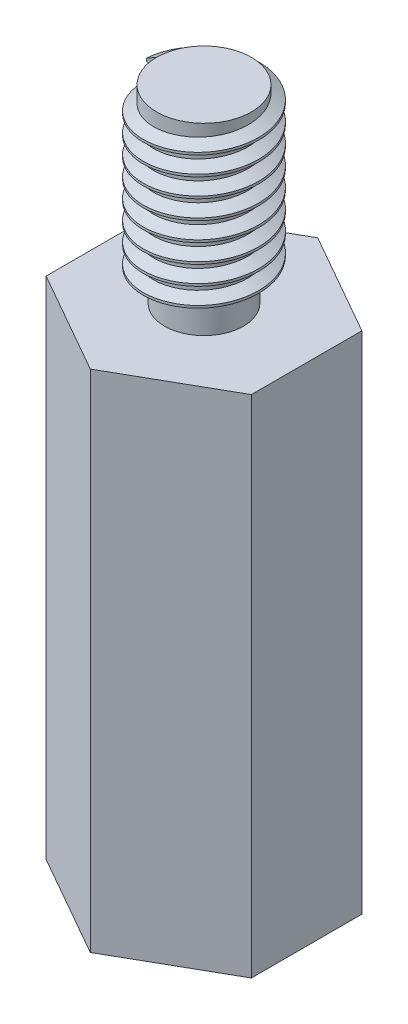
SolidWorks part; units mm, degrees
material "1.4000 (X6Cr13)"
ref_plane "Plan de face" through (0, 0, 0) normal (0, 0, 1) x (1, 0, 0)
ref_plane "Plan de dessus" through (0, 0, 0) normal (0, 1, 0) x (1, 0, 0)
ref_plane "Plan de droite" through (0, 0, 0) normal (1, 0, 0) x (0, 0, -1)
sketch "Esquisse1" plane through (0, 0, 0) normal (0, 1, 0) x (1, 0, 0)
  line L0 (-3.25, 0) -> (3.25, 0) construction
  line L1 (0, 3.6) -> (0, -3.6) construction
  line L2 (-3.25, 1.75) -> (-3.25, -1.75)
  line L3 (0, 3.6) -> (-3.25, 1.75)
  line L4 (-3.25, -1.75) -> (0, -3.6)
  line L5 (3.25, 1.75) -> (3.25, -1.75)
  line L6 (3.25, -1.75) -> (0, -3.6)
  line L7 (0, 3.6) -> (3.25, 1.75)
  point P4 (0, 0)
  point P6 (0, 0)
  point P9 (-3.25, 0)
  dimension "D1" = 6.5
  dimension "D2" = 7.2
  dimension "D3" = 3.5
extrude "Boss.-Extru.1" add sketch "Esquisse1" along normal blind 16
sketch "Esquisse2" plane through (0, 0, 0) normal (0, -1, 0) x (1, 0, 0)
  circle A0 centre (0, 0) radius 1.5
  dimension "D1" = 3
extrude "Enlèv. mat.-Extru.1" cut sketch "Esquisse2" against normal blind 6
sketch "Esquisse3" plane through (0, 16, 0) normal (0, 1, 0) x (1, 0, 0)
  circle A0 centre (0, 0) radius 1.25
  dimension "D1" = 2.5
extrude "Boss.-Extru.2" add sketch "Esquisse3" along normal blind 6
sketch "Esquisse4" plane through (0, 22, 0) normal (0, 1, 0) x (1, 0, 0)
  circle A0 centre (0, 0) radius 1.5
  dimension "D1" = 3
extrude "Boss.-Extru.3" add sketch "Esquisse4" against normal blind 5
thread "Filetage1" pitch 0.6 method extrude profile "Profil de filetage1" start angle 0, offset 0, length 5, pitch 0.6, diameter 3
ref_plane "Plan1" through (-1.5, 22, 0) normal (0, 0, 1) x (-1, 0, 0)
sketch "Profil de filetage1" plane through (-1.5, 22, 0) normal (0, 0, 1) x (-1, 0, 0)
  line L0 (0, 0) -> (0, 0.6) construction
  line L1 (0, 0) -> (0.3248, 0.1875)
  line L2 (0.3248, 0.1875) -> (0.3248, 0.2625)
  line L3 (0.3248, 0.2625) -> (0, 0.45)
  line L4 (0.3248, 0.225) -> (0, 0.225) construction
  line L11 (0, 0) -> (0, 0.45)
  point P2 (0, 0)
  dimension "Pitch" = 0.6
  dimension "Profile_Angle" = 60
  dimension "Profile_Land" = 0.075
  dimension "Profile_Height" = 0.3248
thread "Filetage2" pitch 0.6 method cut profile "Profil de filetage2" start angle 0, offset 0, length 5, pitch 0.6, diameter 3
ref_plane "Plan2" through (1.5, 0, 0) normal (0, 0, 1) x (1, 0, 0)
sketch "Profil de filetage2" plane through (1.5, 0, 0) normal (0, 0, 1) x (1, 0, 0)
  line L0 (0, 0) -> (0, 0.6) construction
  line L1 (0, 0) -> (0.3248, 0.1875)
  line L2 (0.3248, 0.1875) -> (0.3248, 0.2625)
  line L3 (0.3248, 0.2625) -> (0, 0.45)
  line L4 (0.3248, 0.225) -> (0, 0.225) construction
  line L11 (0, 0) -> (0, 0.45)
  point P2 (0, 0)
  dimension "Pitch" = 0.6
  dimension "Profile_Angle" = 60
  dimension "Profile_Land" = 0.075
  dimension "Profile_Height" = 0.3248
